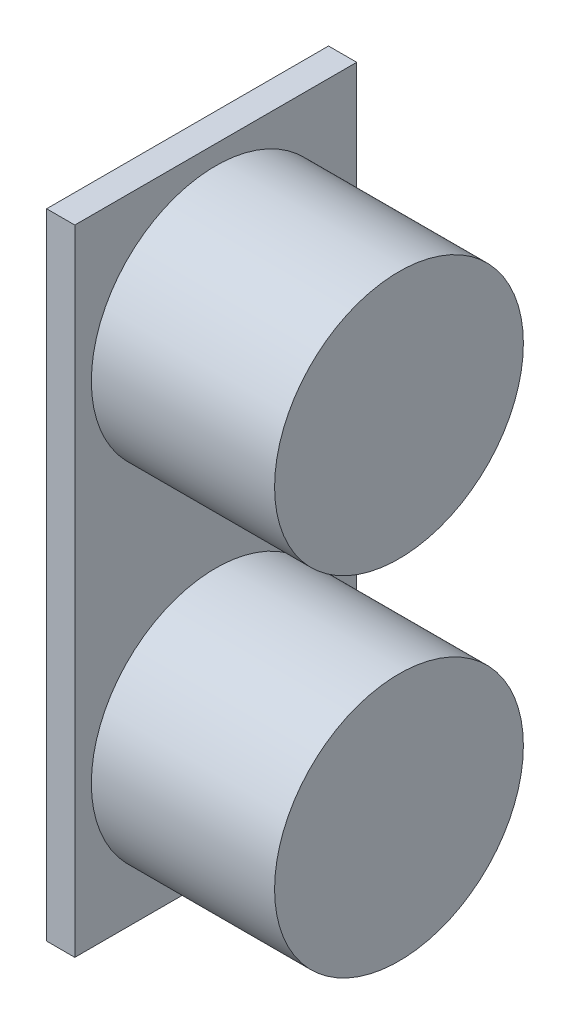
SolidWorks part; units mm, degrees
ref_plane "Front Plane" through (0, 0, 0) normal (1, 0, 0) x (0, 1, 0)
ref_plane "Top Plane" through (0, 0, 0) normal (0, 0, 1) x (0, 1, 0)
ref_plane "Right Plane" through (0, 0, 0) normal (0, 1, 0) x (-1, 0, 0)
sketch "Sketch1" plane through (0, 0, 0) normal (1, 0, 0) x (0, 1, 0)
  line L1 (0, 0) -> (45, 0)
  line L2 (0, 0) -> (0, 20)
  line L3 (0, 20) -> (45, 20)
  line L4 (45, 0) -> (45, 20)
  dimension "D1" = 45
  dimension "D2" = 20
extrude "Boss-Extrude1" add sketch "Sketch1" along normal blind 2
sketch "Sketch2" plane through (2, 0, 0) normal (1, 0, 0) x (0, 1, 0)
  circle A0 centre (10.0963, 10) radius 8.8263
  circle A1 centre (34.8147, 10) radius 8.8263
extrude "Boss-Extrude3" add sketch "Sketch2" along normal blind 13 contours A0
extrude "Boss-Extrude4" add sketch "Sketch2<5>" along normal blind 13 contours A1
sketch "Sketch2<5>" plane through (2, 0, 0) normal (1, 0, 0) x (0, 1, 0) same geometry as "Sketch2"
